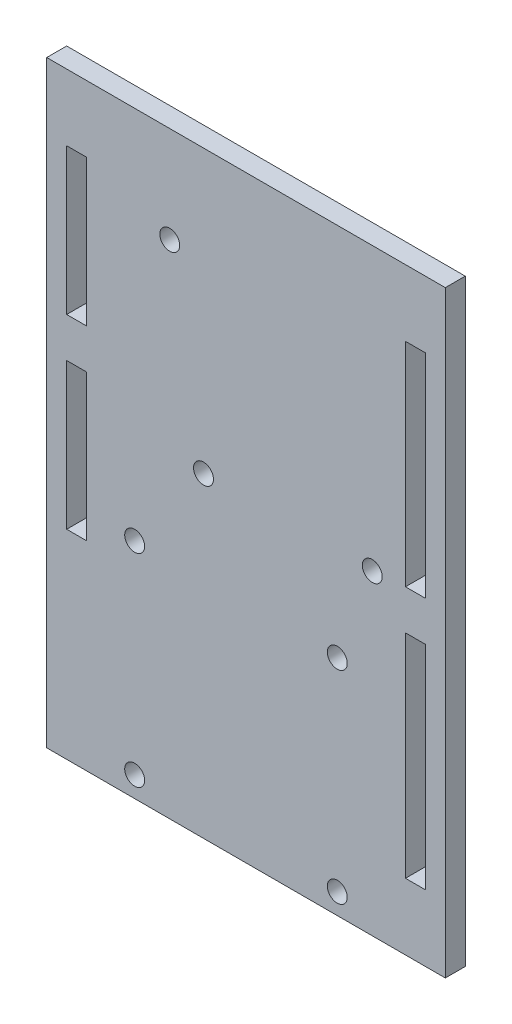
SolidWorks part; units mm, degrees
material "Custom Plastic"
ref_plane "Front Plane" through (0, 0, 0) normal (0, 0, 1) x (1, 0, 0)
ref_plane "Top Plane" through (0, 0, 0) normal (0, 1, 0) x (1, 0, 0)
ref_plane "Right Plane" through (0, 0, 0) normal (1, 0, 0) x (0, 0, -1)
sketch "Sketch1" plane through (0, 0, 0) normal (0, 0, 1) x (1, 0, 0)
  line L1 (-30, 45) -> (30, 45)
  line L2 (-30, 45) -> (-30, -45)
  line L3 (-30, -45) -> (30, -45)
  line L4 (30, 45) -> (30, -45)
  line L5 (-30, 45) -> (30, -45) construction
  line L6 (-30, -45) -> (30, 45) construction
  point P0 (0, 0)
  dimension "D1" = 60
  dimension "D2" = 90
extrude "Boss-Extrude1" add sketch "Sketch1" against normal blind 3
sketch "Sketch3" plane through (0, 0, 0) normal (0, 0, 1) x (1, 0, 0)
  line L0 (30, -45) -> (30, 45) construction
  line L3 (19, 2.56) -> (-6.4, 2.56) construction
  line L4 (30, 45) -> (-30, 45) construction
  circle A0 centre (-11.48, 30.5) radius 1.5
  circle A1 centre (-6.4, 2.56) radius 1.5
  circle A2 centre (19, 2.56) radius 1.5
  dimension "D5" = 3
  dimension "D6" = 3
  dimension "D7" = 3
  dimension "D1" = 27.94
  dimension "D2" = 5.08
  dimension "D3" = 25.4
  dimension "D4" = 14.5
  dimension "D8" = 11
extrude "Cut-Extrude2" cut sketch "Sketch3" against normal blind 3
sketch "Sketch4" plane through (0, 0, 0) normal (0, 0, 1) x (1, 0, 0)
  line L0 (-16.7628, -11.3802) -> (-16.7628, -41.8802) construction
  line L1 (-16.7628, -41.8802) -> (13.7372, -41.8802) construction
  line L2 (13.7372, -41.8802) -> (13.7372, -11.3802) construction
  circle A0 centre (-16.7628, -41.8802) radius 1.5
  circle A1 centre (-16.7628, -11.3802) radius 1.5
  circle A2 centre (13.7372, -41.8802) radius 1.5
  circle A3 centre (13.7372, -11.3802) radius 1.5
  dimension "D3" = 3
  dimension "D1" = 30.5
  dimension "D2" = 30.5
extrude "Cut-Extrude3" cut sketch "Sketch4" against normal through all
sketch "Sketch5" plane through (0, 0, 0) normal (0, 0, 1) x (1, 0, 0)
  line L0 (30, 45) -> (-30, 45) construction
  line L1 (27, -35) -> (24, -35)
  line L2 (27, -35) -> (27, -3)
  line L3 (27, -3) -> (24, -3)
  line L4 (24, -35) -> (24, -3)
  line L5 (27, 3) -> (24, 3)
  line L6 (27, 3) -> (27, 35)
  line L7 (27, 35) -> (24, 35)
  line L8 (24, 3) -> (24, 35)
  line L10 (30, -45) -> (30, 45) construction
  dimension "D1" = 6
  dimension "D2" = 32
  dimension "D3" = 10
  dimension "D4" = 3
  dimension "D5" = 3
extrude "Cut-Extrude4" cut sketch "Sketch5" against normal through all
sketch "Sketch6" plane through (0, 0, 0) normal (0, 0, 1) x (1, 0, 0)
  line L0 (-30, 45) -> (-30, -45) construction
  line L1 (-24, -15) -> (-27, -15)
  line L2 (-24, -15) -> (-24, 7)
  line L3 (-24, 7) -> (-27, 7)
  line L4 (-27, -15) -> (-27, 7)
  line L5 (-24, 13) -> (-27, 13)
  line L6 (-24, 13) -> (-24, 35)
  line L7 (-24, 35) -> (-27, 35)
  line L8 (-27, 13) -> (-27, 35)
  line L9 (-30, -45) -> (30, -45) construction
  line L10 (30, 45) -> (-30, 45) construction
  dimension "D1" = 3
  dimension "D2" = 3
  dimension "D3" = 30
  dimension "D4" = 6
  dimension "D5" = 10
extrude "Cut-Extrude5" cut sketch "Sketch6" against normal through all
